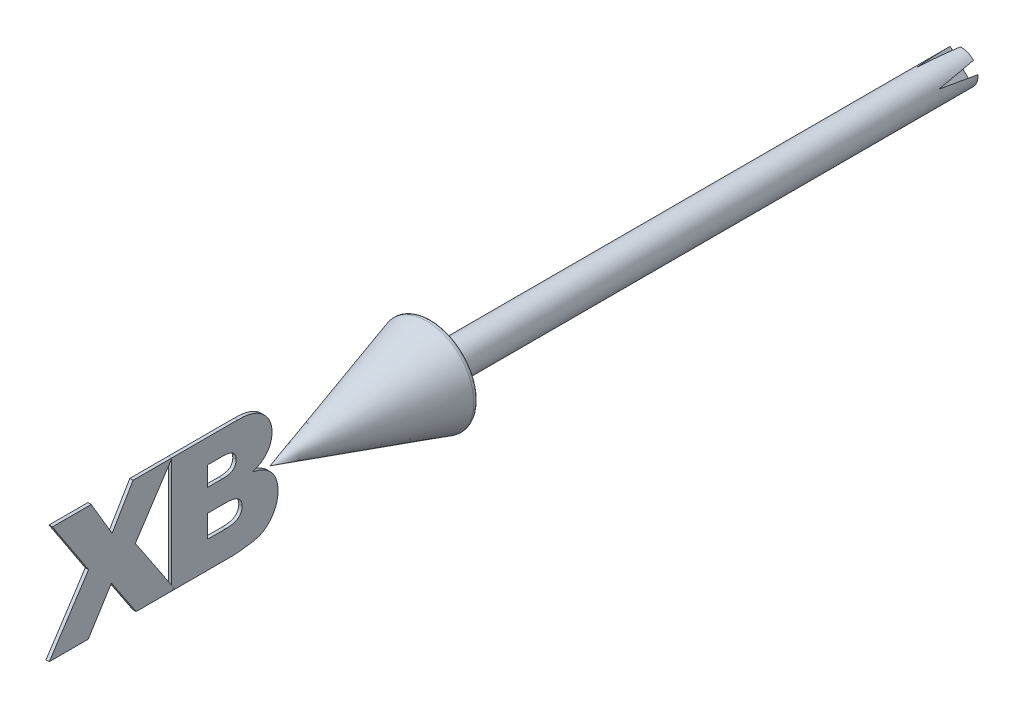
SolidWorks part; units mm, degrees
ref_plane "Front" through (0, 0, 0) normal (0, 0, 1) x (1, 0, 0)
ref_plane "Top" through (0, 0, 0) normal (0, 1, 0) x (1, 0, 0)
ref_plane "Right" through (0, 0, 0) normal (1, 0, 0) x (0, 0, -1)
sketch "Sketch1" plane through (0, 0, 0) normal (1, 0, 0) x (0, 0, -1)
  line L0 (-200, 0) -> (10, 0)
  line L1 (-155.7735, -5) -> (10, -5)
  line L2 (-200, 0) -> (-219.757, 0) construction
  line L3 (-155.7735, -5) -> (-150, -15)
  line L4 (-150, -15) -> (-200, 0)
  line L5 (10, 0) -> (10, -5)
  line L6 (0, 15.7501) -> (0, -15.7501) construction
  dimension "Thickness" = 10
  dimension "D3" = 50
  dimension "D4" = 15
  dimension "D5" = 60
  dimension "Length" = 200
  dimension "TailLength" = 10
revolve "Revolve1" add sketch "Sketch1" angle 360 about L2
fillet "Fillet1" radius 1 1 edges at (0, 15, 150)
ref_axis "CoordinateAxis" through (0, 0, 281.4227) along (0, 0, -1)
sketch "Sketch7" plane through (0, 0, 0) normal (1, 0, 0) x (0, 0, -1)
  line L0 (-386.9, 0) -> (28.9, 0) construction
  text T0 "Z" font "Arial Black" height 35
  dimension "D1" = 68
  dimension "D2" = 17.5
sketch "Sketch10" plane through (0, 0, 0) normal (1, 0, 0) x (0, 0, -1)
  text T0 "X" font "Arial Black" height 35
  dimension "D1" = 17.5
  dimension "D2" = 68
extrude "X" add sketch "Sketch10" along normal mid plane 1
sketch "Sketch11" plane through (0, 0, 0) normal (1, 0, 0) x (0, 0, -1)
  text T0 "Y" font "Arial Black" height 35
  dimension "D1" = 68
  dimension "D2" = 17.5
extrude "Y" [suppressed] add sketch "Sketch11" along normal mid plane 1
extrude "Z" [suppressed] add sketch "Sketch7" along normal mid plane 1
sketch "Sketch8" plane through (0, 0, 0) normal (1, 0, 0) x (0, 0, -1)
  line L0 (-386.9, 0) -> (28.9, 0) construction
  text T0 "0" font "Arial Black" height 35
  dimension "D1" = 17.5
  dimension "D2" = 34
extrude "0" [suppressed] add sketch "Sketch8" along normal blind 1
sketch "Sketch12" plane through (0, 0, 0) normal (1, 0, 0) x (0, 0, -1)
  text T0 "1" font "Arial Black" height 35
  dimension "D1" = 17.5
  dimension "D2" = 34
extrude "1" [suppressed] add sketch "Sketch12" along normal mid plane 1
sketch "Sketch13" plane through (0, 0, 0) normal (1, 0, 0) x (0, 0, -1)
  text T0 "2" font "Arial Black" height 35
  dimension "D1" = 34
  dimension "D2" = 17.5
extrude "2" [suppressed] add sketch "Sketch13" along normal mid plane 1
sketch "Sketch21" plane through (0, 0, 0) normal (1, 0, 0) x (0, 0, -1)
  text T0 "3" font "Arial Black" height 35
  dimension "D1" = 34
  dimension "D2" = 17.5
extrude "3" [suppressed] add sketch "Sketch21" along normal mid plane 1
sketch "Sketch14" plane through (0, 0, 0) normal (1, 0, 0) x (0, 0, -1)
  text T0 "4" font "Arial Black" height 35
  dimension "D1" = 34
  dimension "D2" = 17.5
extrude "4" [suppressed] add sketch "Sketch14" along normal mid plane 1
sketch "Sketch16" plane through (0, 0, 0) normal (1, 0, 0) x (0, 0, -1)
  text T0 "5" font "Arial Black" height 35
  dimension "D1" = 34
  dimension "D2" = 17.5
extrude "5" [suppressed] add sketch "Sketch16" along normal mid plane 1
sketch "Sketch17" plane through (0, 0, 0) normal (1, 0, 0) x (0, 0, -1)
  text T0 "6" font "Arial Black" height 35
  dimension "D1" = 34
  dimension "D2" = 17.5
extrude "6" [suppressed] add sketch "Sketch17" along normal mid plane 1
sketch "Sketch18" plane through (0, 0, 0) normal (1, 0, 0) x (0, 0, -1)
  text T0 "7" font "Arial Black" height 35
  dimension "D1" = 34
  dimension "D2" = 17.5
extrude "7" [suppressed] add sketch "Sketch18" along normal mid plane 1
sketch "Sketch19" plane through (0, 0, 0) normal (1, 0, 0) x (0, 0, -1)
  text T0 "B" font "Arial Black" height 35
  dimension "D1" = 34
  dimension "D2" = 17.5
extrude "B" add sketch "Sketch19" along normal mid plane 1
sketch "Sketch20" plane through (0, 0, 0) normal (1, 0, 0) x (0, 0, -1)
  text T0 "T" font "Arial Black" height 35
  dimension "D1" = 34
  dimension "D2" = 17.5
extrude "T" [suppressed] add sketch "Sketch20" along normal mid plane 1
sketch "Sketch23" plane through (0, 0, -10) normal (0, 0, -1) x (-1, 0, 0)
  line L0 (0, 0) -> (-5, 0) construction
  line L1 (0, 0) -> (-3.5355, -3.5355)
  line L2 (0, 0) -> (-3.5355, 3.5355)
  circle A0 centre (0, 0) radius 5 construction
  circle A1 centre (0, 0) radius 5 construction
sketch "Sketch25" plane through (0, 0, 0) normal (1, 0, 0) x (0, 0, -1)
  line L0 (10, 0) -> (-13.5232, 5)
  line L3 (10, 5) -> (-155.7735, 5) construction
  line L4 (15.7501, 0) -> (-15.7501, 0) construction
  dimension "D1" = 12
ref_plane "Plane1" through (-1.0393, 1.0393, -0.2209) normal (0.6993, -0.6993, 0.1486) x (0.6667, 0.7129, 0.2175)
sketch "Sketch26" plane through (-1.0393, 1.0393, -0.2209) normal (0.6993, -0.6993, 0.1486) x (0.6667, 0.7129, 0.2175)
  line L0 (-10.8882, -32.1589) -> (-1.2038, -34.3423)
  line L1 (-10.8882, -32.1589) -> (2.2247, 1.7202)
  line L2 (2.2247, 1.7202) -> (-1.2038, -34.3423)
extrude "Cut-Extrude1" cut sketch "Sketch26" against normal through all
pattern_circular "CirPattern1" count 4 over 360 about axis through (0, 0, 281.4227) along (0, 0, -1) of "Cut-Extrude1"
